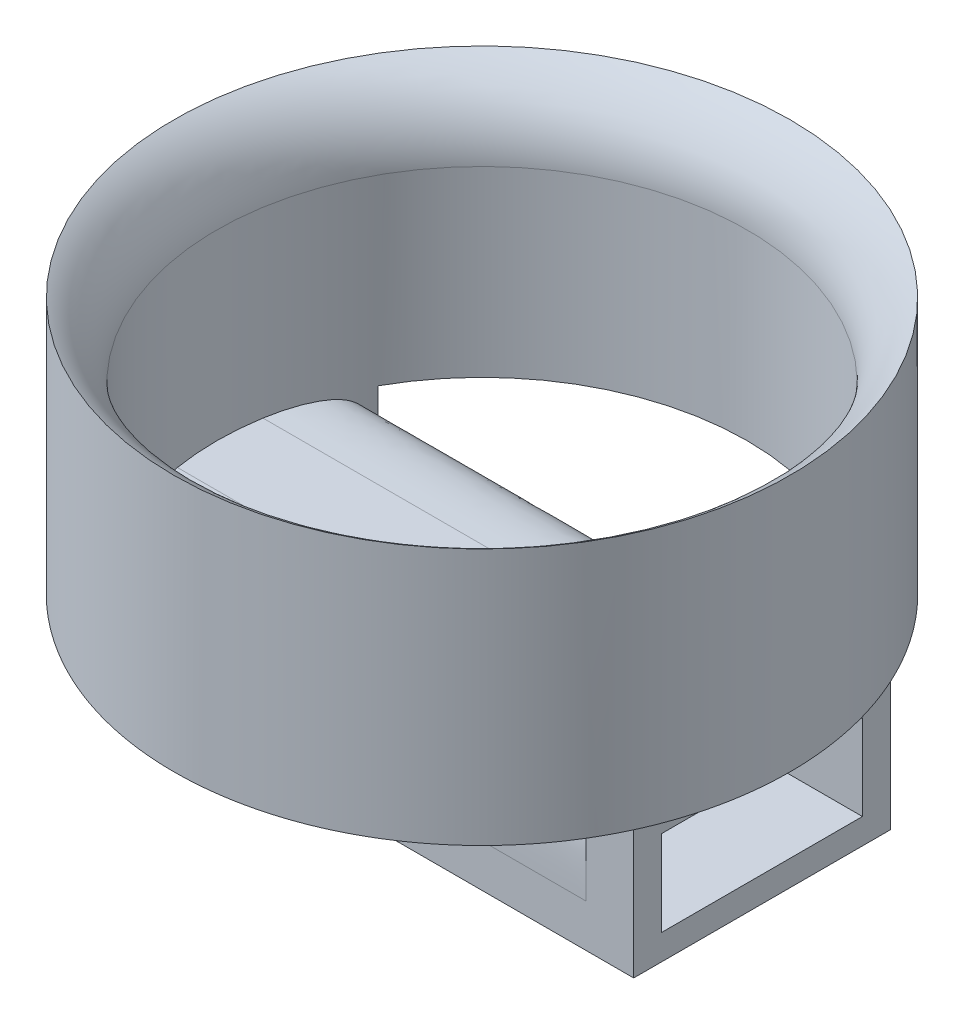
SolidWorks part; units mm, degrees
ref_plane "前基準面" through (0, 0, 0) normal (0, 0, 1) x (1, 0, 0)
ref_plane "上基準面" through (0, 0, 0) normal (0, 1, 0) x (1, 0, 0)
ref_plane "右基準面" through (0, 0, 0) normal (1, 0, 0) x (0, 0, -1)
sketch "草圖1" plane through (0, 0, 0) normal (0, 1, 0) x (1, 0, 0)
  circle A0 centre (0, 0) radius 36
  dimension "D1" = 72
extrude "填料-伸長1" add sketch "草圖1" along normal blind 30
sketch "草圖2" plane through (0, 30, 0) normal (0, 1, 0) x (1, 0, 0)
  circle A0 centre (0, 0) radius 31
  dimension "D1" = 62
extrude "除料-伸長1" cut sketch "草圖2" against normal blind 30
fillet "圓角1" radius 10 1 edges at (0, 30, 31)
sketch "草圖11" plane through (0, 0, 0) normal (0, 1, 0) x (1, 0, 0)
  line L0 (-1000, 0) -> (49000, 0) construction
  line L1 (0, -1000) -> (0, 49000) construction
  line L3 (-32.7258, 15) -> (32.7258, 15)
  line L4 (-32.7258, 15) -> (-32.7258, -15)
  line L5 (-32.7258, -15) -> (32.7258, -15)
  line L6 (32.7258, 15) -> (32.7258, -15)
  line L7 (-32.7258, 15) -> (32.7258, -15) construction
  line L8 (-32.7258, -15) -> (32.7258, 15) construction
  point P4 (0, 0)
  dimension "D1" = 30
extrude "填料-伸長8" add sketch "草圖11" against normal blind 15
sketch "草圖13" plane through (-32.7258, 0, 0) normal (-1, 0, 0) x (0, 0, 1)
  line L0 (0, -1000) -> (0, 49000) construction
  line L1 (-1000, 0) -> (49000, 0) construction
  line L2 (1.724, -7.0203) -> (49000, -7.0203) construction
sketch "草圖16" plane through (-32.7258, 0, 0) normal (-1, 0, 0) x (0, 0, 1)
  line L0 (0, -201000) -> (0, 249000) construction
  line L1 (-11.725, -2.0203) -> (11.725, -2.0203)
  line L2 (-11.725, -2.0203) -> (-11.725, -12.0203)
  line L3 (-11.725, -12.0203) -> (11.725, -12.0203)
  line L4 (11.725, -2.0203) -> (11.725, -12.0203)
  line L5 (-11.725, -2.0203) -> (11.725, -12.0203) construction
  line L6 (-11.725, -12.0203) -> (11.725, -2.0203) construction
  line L7 (-199998.276, -7.0203) -> (249000, -7.0203) construction
  point P0 (0, -7.0203)
  dimension "D1" = 10
  dimension "D2" = 23.45
extrude "除料-伸長3" cut sketch "草圖16" against normal through all
sketch "草圖18" plane through (-32.7258, 0, 0) normal (-1, 0, 0) x (0, 0, 1)
  line L5 (-1011.725, -6.6247) -> (48988.275, -6.6247) construction
  line L10 (-1011.725, -7.6247) -> (48988.275, -7.6247) construction
sketch "草圖19" plane through (-32.7258, 0, 0) normal (-1, 0, 0) x (0, 0, 1)
  line L0 (-11.725, -6.6247) -> (-12.725, -6.6247)
  line L1 (-201011.725, -6.6247) -> (248988.275, -6.6247) construction
  line L2 (-11.725, -2.0203) -> (-11.725, -12.0203) construction
  line L3 (-12.725, -6.6247) -> (-12.725, -5.6247)
  line L4 (-12.725, -5.6247) -> (-13.725, -5.6247)
  line L5 (-13.725, -5.6247) -> (-13.725, -8.6248)
  line L6 (-13.725, -8.6248) -> (-12.725, -8.6248)
  line L7 (-12.725, -8.6248) -> (-12.725, -7.6247)
  line L8 (-201011.725, -7.6247) -> (248988.275, -7.6247) construction
  line L9 (-12.725, -7.6247) -> (-11.725, -7.6247)
  line L10 (-11.725, -7.6247) -> (-11.725, -6.6247)
extrude "除料-伸長4" cut sketch "草圖19" against normal blind 58
fillet "圓角2" radius 10 2 edges at (0, 0, 15) (0, 0, -15) conic rho 0.7
